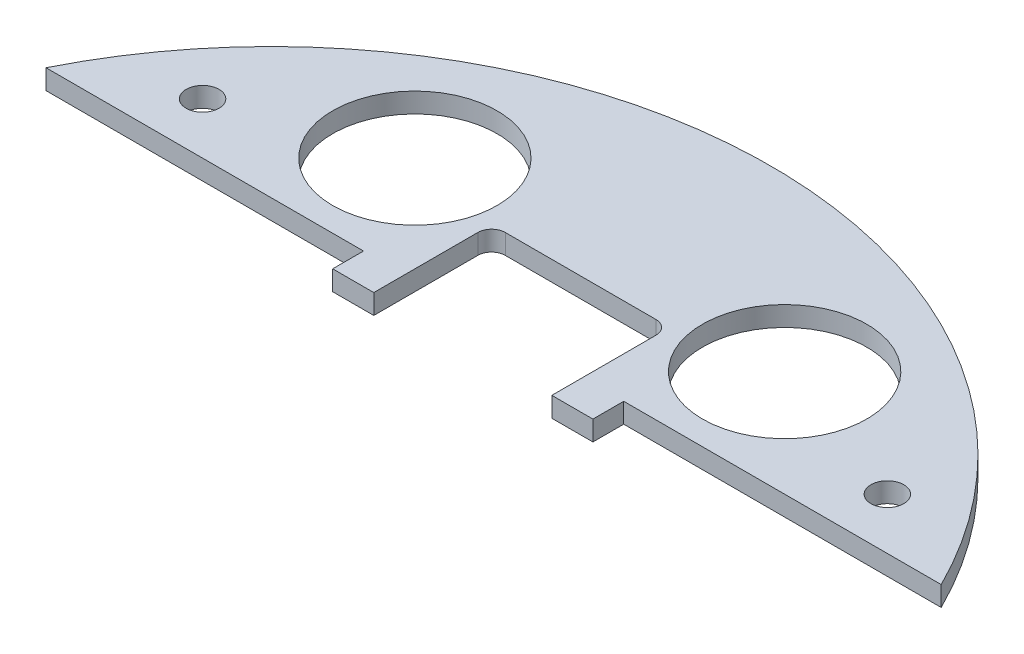
SolidWorks part; units mm, degrees
material "Acrylic (Medium-high impact)"
ref_plane "Front Plane" through (0, 0, 0) normal (0, 0, 1) x (1, 0, 0)
ref_plane "Top Plane" through (0, 0, 0) normal (0, 1, 0) x (1, 0, 0)
ref_plane "Right Plane" through (0, 0, 0) normal (1, 0, 0) x (0, 0, -1)
sketch "Sketch1" plane through (0, 0, 0) normal (0, 1, 0) x (1, 0, 0)
  line L0 (0, -85) -> (-32.7511, -65.2408) construction
  line L1 (0, -85) -> (0, 0) construction
  arc A0 (36.8566, -63.0126) -> (-36.8566, -63.0126) centre (0, 0) ccw
  arc A1 (30.3631, -61.7375) -> (-30.3631, -61.7375) centre (0, -85) ccw
  arc A2 (36.8566, -63.0126) -> (30.3631, -61.7375) centre (34.3322, -58.6967) cw
  arc A3 (-30.3631, -61.7375) -> (-36.8566, -63.0126) centre (-34.3322, -58.6967) cw
  dimension "D1" = 146
  dimension "D2" = 76.5
  dimension "D4" = 5
  dimension "D3" = 85
extrude "Boss-Extrude1" add sketch "Sketch1" along normal blind 2.9
sketch "solenoid placement" plane through (0, 2.9, 0) normal (0, 1, 0) x (1, 0, 0)
  line L4 (-19, -36) -> (19, -36)
  line L5 (-19, 28) -> (-19, -36)
  line L6 (19, 28) -> (-19, 28)
  line L7 (19, -36) -> (19, 28)
  line L8 (-19, -36) -> (19, -36)
  line L9 (-19, 28) -> (-19, -36)
  line L10 (19, 28) -> (-19, 28)
  line L11 (19, -36) -> (19, 28)
  dimension "D1" = 0
extrude "Cut-Extrude1" cut sketch "solenoid placement" against normal through all
sketch "Sketch4" plane through (0, 2.9, 0) normal (0, 1, 0) x (1, 0, 0)
  line L6 (-13, 28) -> (13, 28)
  line L7 (13, 28) -> (13, 43.2)
  line L8 (11, 45.2) -> (-11, 45.2)
  line L9 (-13, 43.2) -> (-13, 28)
  line L10 (-13, 28) -> (13, 28)
  line L11 (13, 28) -> (13, 43.2)
  line L12 (11, 45.2) -> (-11, 45.2)
  line L13 (-13, 43.2) -> (-13, 28)
  arc A4 (13, 43.2) -> (11, 45.2) centre (11, 43.2) ccw
  arc A5 (13, 43.2) -> (11, 45.2) centre (11, 43.2) ccw
  arc A6 (-11, 45.2) -> (-13, 43.2) centre (-11, 43.2) ccw
  arc A7 (-11, 45.2) -> (-13, 43.2) centre (-11, 43.2) ccw
  dimension "D1" = 0
extrude "Cut-Extrude4" cut sketch "Sketch4" against normal through all
sketch "Sketch5" plane through (0, 2.9, 0) normal (0, 1, 0) x (1, 0, 0)
  circle A1 centre (-27, 48) radius 12
  circle A2 centre (-27, 48) radius 12
  circle A3 centre (27, 48) radius 12
  circle A4 centre (27, 48) radius 12
  dimension "D1" = 0
  dimension "D2" = 0
extrude "Cut-Extrude5" cut sketch "Sketch5" against normal through all
sketch "Sketch6" plane through (0, 2.9, 0) normal (0, 1, 0) x (1, 0, 0)
  circle A1 centre (40, -40) radius 2.4
  circle A2 centre (40, -40) radius 2.4
  circle A3 centre (-40, -40) radius 2.4
  circle A4 centre (-40, -40) radius 2.4
  circle A5 centre (-50, 40) radius 2.4
  circle A6 centre (-50, 40) radius 2.4
  circle A7 centre (50, 40) radius 2.4
  circle A8 centre (50, 40) radius 2.4
  dimension "D1" = 0
  dimension "D2" = 0
  dimension "D3" = 0
  dimension "D4" = 0
extrude "Cut-Extrude6" cut sketch "Sketch6" against normal through all
sketch "Sketch3" plane through (0, 2.9, 0) normal (0, 1, 0) x (1, 0, 0)
  line L0 (-19, 28) -> (19, 28)
  line L1 (-73, -32.5) -> (73, -32.5)
  line L2 (-73, -32.5) -> (-73, 32.5)
  line L3 (-73, 32.5) -> (-19, 32.5)
  line L4 (73, -32.5) -> (73, 32.5)
  line L5 (-73, -32.5) -> (73, 32.5) construction
  line L6 (-73, 32.5) -> (73, -32.5) construction
  line L7 (19, 28) -> (19, 32.5)
  line L8 (-19, 28) -> (-19, 32.5)
  line L9 (19, 32.5) -> (73, 32.5)
  arc A0 (36.8566, -63.0126) -> (-36.8566, -63.0126) centre (0, 0) ccw construction
  point P0 (0, 0)
  dimension "D1" = 65
extrude "Cut-Extrude3" cut sketch "Sketch3" against normal through all
sketch "Sketch8" plane through (0, 2.9, 0) normal (0, 1, 0) x (1, 0, 0)
  line L4 (5, 0) -> (-5, 0)
  line L5 (5, -62.8025) -> (5, 0)
  line L6 (-5, -62.8025) -> (5, -62.8025)
  line L7 (-5, 0) -> (-5, -62.8025)
  line L8 (5, 0) -> (-5, 0)
  line L9 (5, -62.8025) -> (5, 0)
  line L10 (-5, -62.8025) -> (5, -62.8025)
  line L11 (-5, 0) -> (-5, -62.8025)
  dimension "D1" = 0
extrude "Cut-Extrude9" cut sketch "Sketch8" against normal through all and the other way through all
delete or keep bodies "Body-Delete/Keep 1" type delete bodies bodies 116 117
equation "\"smallPulleyTeeth\"= 15"
equation "\"largePulleyTeeth\"= 30"
equation "\"eighthThick\"= 2.9mm"
equation "\"sixteenthThick\" = 1.7mm"
equation "\"quarterThick\"=6.0mm"
equation "\"OD\" = 146mm"
equation "\"puckAngle\" = 60.5deg"
equation "\"D1@Sketch1\"=\"OD\""
equation "\"puckDiam\" = 76.5mm"
equation "\"D2@Sketch1\"=\"puckDiam\""
equation "\"D1@Boss-Extrude1\"=\"eighthThick\""
equation "\"axlePress\" = 5.9mm"
equation "\"press\" = 0.2mm"
equation "\"wheelClear\" = 0.3mm"
equation "\"10-32clear\" = 4.8mm"
equation "\"6-32clear\" = 3.3mm"
equation "\"8-32clear\" = 4.0mm"
equation "\"wheelHeight\" = 22mm"
equation "\"wheelWell\" = 65mm"
equation "\"D1@Sketch3\"=\"wheelWell\""
equation "\"puckDist\" = 85mm"
equation "\"scoopFillet\" = 5mm"
equation "\"4-40clear\" = 3.0mm"
equation "\"D3@Sketch1\"=\"puckDist\""
equation "\"D4@Sketch1\"=\"scoopFillet\""
